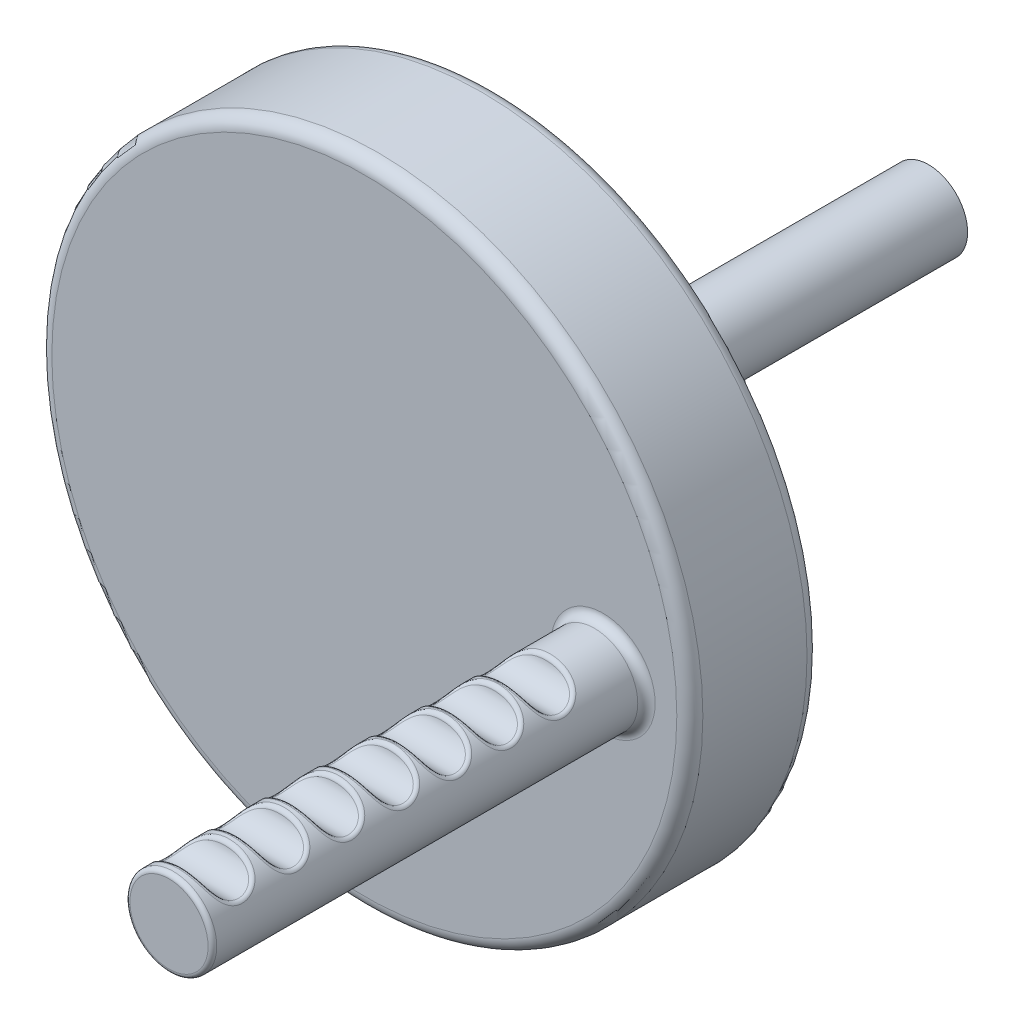
SolidWorks part; units mm, degrees
ref_plane "Front Plane" through (0, 0, 0) normal (0, 0, 1) x (1, 0, 0)
ref_plane "Top Plane" through (0, 0, 0) normal (0, 1, 0) x (1, 0, 0)
ref_plane "Right Plane" through (0, 0, 0) normal (1, 0, 0) x (0, 0, -1)
sketch "Sketch1" plane through (0, 0, 0) normal (0, 0, 1) x (1, 0, 0)
  circle A0 centre (0, 0) radius 9
  dimension "D1" = 18
extrude "Boss-Extrude1" add sketch "Sketch1" along normal mid plane 100
sketch "Sketch2" plane through (0, 0, -50) normal (0, 0, -1) x (-1, 0, 0)
  line L1 (8.4853, -3) -> (5.1753, -3)
  line L3 (8.4853, 3) -> (5.1753, 3)
  line L4 (5.1753, -3) -> (5.1753, 3)
  circle A0 centre (0, 0) radius 9 construction
  arc A1 (8.4853, -3) -> (8.4853, 3) centre (0, 0) ccw
  dimension "D1" = 6
  dimension "D2" = 3.31
extrude "Cut-Extrude1" cut sketch "Sketch2" against normal blind 40
sketch "Sketch3" plane through (0, 0, 50) normal (0, 0, 1) x (1, 0, 0)
  circle A0 centre (0, 0) radius 75
  dimension "D1" = 150
extrude "Boss-Extrude2" add sketch "Sketch3" along normal blind 30
sketch "Sketch4" plane through (0, 0, 80) normal (0, 0, 1) x (1, 0, 0)
  circle A0 centre (55, 0) radius 10
  dimension "D1" = 20
  dimension "D2" = 55
extrude "Boss-Extrude3" add sketch "Sketch4" along normal blind 100
ref_plane "Plane1" through (55, 0, 0) normal (1, 0, 0) x (0, 0, -1)
sketch "Sketch5" plane through (55, 0, 0) normal (1, 0, 0) x (0, 0, -1)
  line L0 (-80, 10) -> (-180, 10) construction
  line L1 (-104.6982, 17.3823) -> (-74.3137, 17.3823)
  line L2 (-167.0029, 10) -> (-164.3565, 10)
  line L3 (-154.3594, 10) -> (-151.7131, 10)
  line L4 (-141.7159, 10) -> (-139.0696, 10)
  line L5 (-177, 10) -> (-167.0029, 10)
  line L6 (-164.3565, 10) -> (-154.3594, 10)
  line L7 (-151.7131, 10) -> (-141.7159, 10)
  line L8 (-139.0696, 10) -> (-129.0724, 10)
  line L9 (-127.0724, 10) -> (-117.0753, 10)
  line L10 (-115.0753, 10) -> (-105.0782, 10)
  line L11 (-103.0782, 10) -> (-93.081, 10)
  arc A0 (-177, 10) -> (-167.0029, 10) centre (-172.0014, 10.1195) ccw
  arc A1 (-164.3565, 10) -> (-154.3594, 10) centre (-159.358, 10.1195) ccw
  arc A2 (-151.7131, 10) -> (-141.7159, 10) centre (-146.7145, 10.1195) ccw
  arc A3 (-139.0696, 10) -> (-129.0724, 10) centre (-134.071, 10.1195) ccw
  arc A4 (-127.0724, 10) -> (-117.0753, 10) centre (-122.0739, 10.1195) ccw
  arc A5 (-115.0753, 10) -> (-105.0782, 10) centre (-110.0767, 10.1195) ccw
  arc A6 (-103.0782, 10) -> (-93.081, 10) centre (-98.0796, 10.1195) ccw
  dimension "D1" = 5
  dimension "D2" = 3
  dimension "D3" = 4
  dimension "D4" = 4
  dimension "D5" = 2
extrude "Cut-Extrude2" cut sketch "Sketch5" against normal through all both and the other way through all contours L5 A0 | L6 A1 | L7 A2 | L8 A3 | L9 A4 | L10 A5 | L11 A6 region at (55, 7.9327, 134.071) region at (55, 7.9327, 146.7145) region at (55, 7.9327, 159.358) region at (55, 7.9327, 172.0014)
fillet "Fillet1" radius 1 8 edges at (53.6789, 9.9123, 139.0667) (53.6789, 9.9123, 151.7102) (53.6789, 9.9123, 164.3537) (53.6789, 9.9123, 176.9971) (65, 0, 180) (53.6789, 9.9123, 103.0753) (53.6789, 9.9123, 115.0724) (53.6789, 9.9123, 127.0696)
fillet "Fillet2" radius 2 2 edges at (65, 0, 80) (9, 0, 50)
fillet "Fillet3" radius 3 2 edges at (75, 0, 50) (75, 0, 80)
